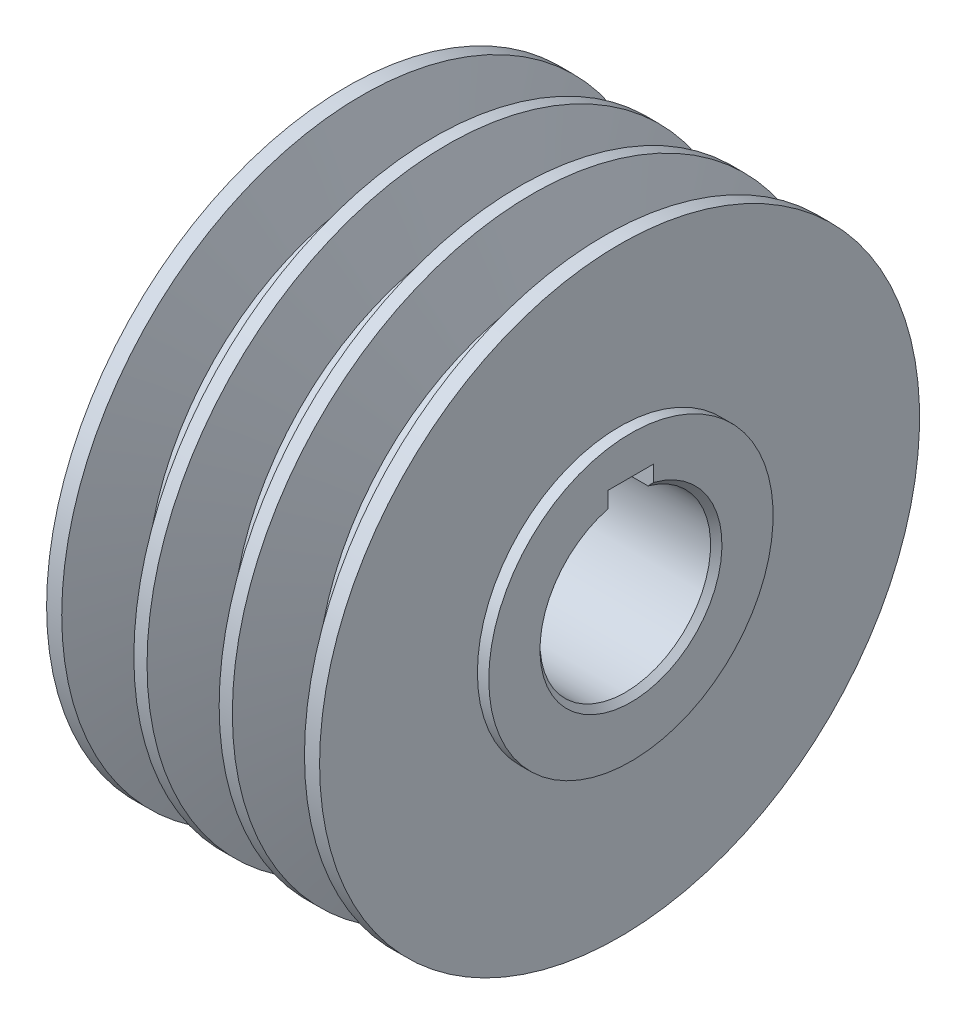
SolidWorks part; units mm, degrees
ref_plane "前视基准面" through (0, 0, 0) normal (0, 0, 1) x (1, 0, 0)
ref_plane "上视基准面" through (0, 0, 0) normal (0, 1, 0) x (1, 0, 0)
ref_plane "右视基准面" through (0, 0, 0) normal (1, 0, 0) x (0, 0, -1)
sketch "草图1" plane through (0, 0, 0) normal (0, 0, 1) x (1, 0, 0)
  line L0 (0, 0) -> (64.8368, 0) construction
  line L1 (0, 15) -> (0, 52.75)
  line L2 (0, 52.75) -> (48, 52.75)
  line L3 (48, 52.75) -> (48, 25)
  line L4 (48, 25) -> (50, 25)
  line L5 (50, 25) -> (50, 15)
  line L6 (50, 15) -> (0, 15)
  line L7 (2.6592, 52.75) -> (6.1599, 41.3) construction
  line L8 (6.1599, 41.3) -> (11.8401, 41.3) construction
  line L9 (11.8401, 41.3) -> (15.3408, 52.75) construction
  line L10 (0, 50) -> (48, 50) construction
  line L11 (9, 41.3) -> (9, 15) construction
  point P17 (3.5, 50)
  point P18 (14.5, 50)
  dimension "d2" = 105.5
  dimension "L" = 50
  dimension "B" = 48
  dimension "d" = 30
  dimension "d1" = 50
  dimension "dd" = 100
  dimension "f" = 9
  dimension "槽轮角" = 34
  dimension "bd" = 11
  dimension "hf" = 8.7
  dimension "ha" = 2.75
revolve "旋转1" add sketch "草图1" angle 360 about L0
sketch "草图2" plane through (0, 0, 0) normal (0, 0, 1) x (1, 0, 0)
  line L0 (11.8401, 41.3) -> (15.3408, 52.75) construction
  line L1 (6.1599, 41.3) -> (11.8401, 41.3) construction
  line L2 (2.6592, 52.75) -> (6.1599, 41.3) construction
  line L3 (11.8401, 41.3) -> (15.3408, 52.75)
  line L4 (6.1599, 41.3) -> (11.8401, 41.3)
  line L5 (2.6592, 52.75) -> (6.1599, 41.3)
  line L6 (2.6592, 52.75) -> (15.3408, 52.75)
  line L7 (0, 0) -> (48, 0) construction
  line L8 (48, -25) -> (48, 25) construction
revolve "切除-旋转1" cut sketch "草图2" angle 360 about L7
pattern_linear "阵列(线性)1" count 3 spacing 15 along (1, 0, 0) of "切除-旋转1"
chamfer "倒角1" distance 1 angle 45 2 edges at (50, 0, 15) (0, 0, 15)
sketch "草图4" plane through (0, 0, 0) normal (-1, 0, 0) x (0, 0, 1)
  line L1 (-4, 14.4568) -> (4, 14.4568)
  line L2 (-4, 14.4568) -> (-4, 18.3)
  line L3 (-4, 18.3) -> (4, 18.3)
  line L4 (4, 14.4568) -> (4, 18.3)
  circle A0 centre (0, 0) radius 15 construction
  point P6 (0.7, 18.3)
  dimension "键槽高度" = 18.3
  dimension "键槽宽度" = 8
  dimension "t1" = 3.3
extrude "切除-拉伸1" cut sketch "草图4" against normal through all
equation "\"B@草图1\" =  ( \"z@阵列(线性)1\" - 1 )  * \"e@阵列(线性)1\" +2 *  \"f@草图1\""
equation "\"键槽高度@草图4\" = \"d@草图1\" / 2  + \"t1@草图4\""
